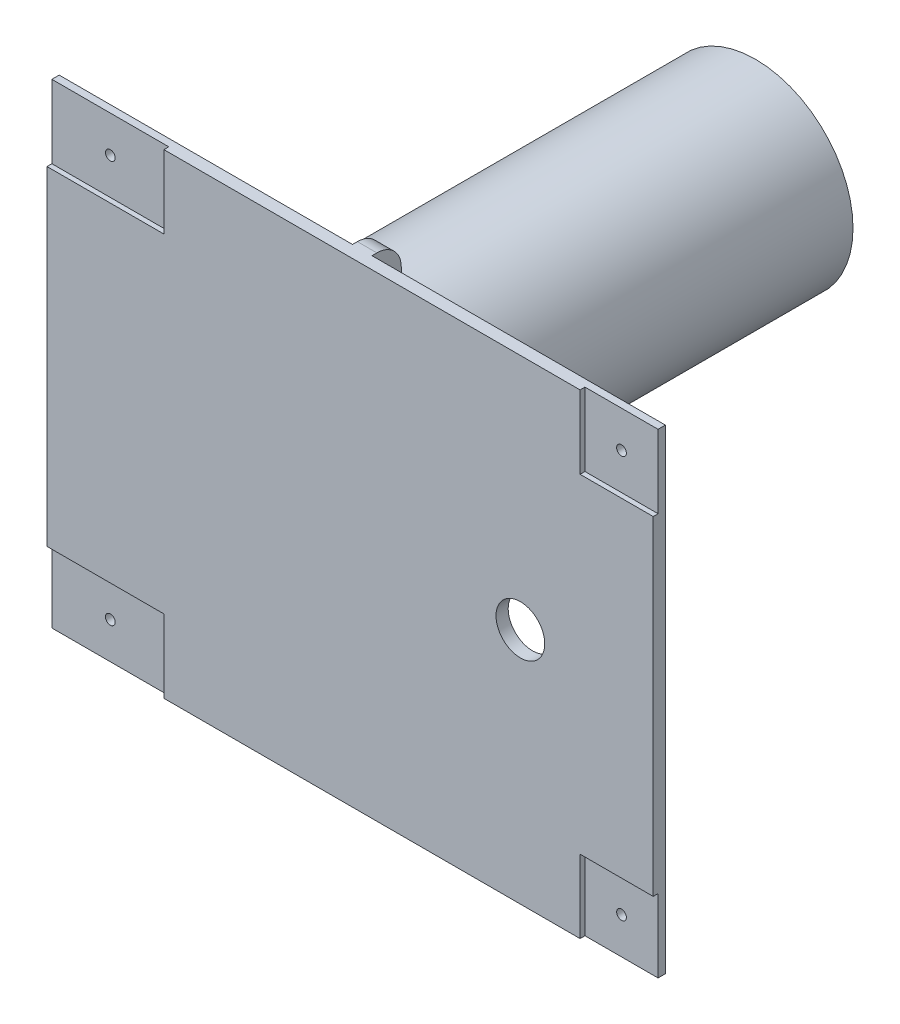
SolidWorks part; units mm, degrees
ref_plane "Alzado" through (0, 0, 0) normal (0, 0, 1) x (1, 0, 0)
ref_plane "Planta" through (0, 0, 0) normal (0, 1, 0) x (1, 0, 0)
ref_plane "Vista lateral" through (0, 0, 0) normal (1, 0, 0) x (0, 0, -1)
sketch "Croquis1" plane through (0, 0, 0) normal (0, 0, 1) x (1, 0, 0)
  line L1 (-117.2917, 97.7627) -> (131.4683, 97.7627)
  line L2 (-117.2917, 97.7627) -> (-117.2917, -97.2373)
  line L3 (-117.2917, -97.2373) -> (131.4683, -97.2373)
  line L4 (131.4683, 97.7627) -> (131.4683, -97.2373)
  dimension "D1" = 248.76
  dimension "D2" = 195
extrude "Saliente-Extruir1" add sketch "Croquis1" along normal blind 5
sketch "Croquis2" plane through (0, 0, 5) normal (0, 0, 1) x (1, 0, 0)
  line L0 (-117.2917, 0.2627) -> (131.4683, 0.2627) construction
  line L1 (-117.2917, 97.7627) -> (-117.2917, -97.2373) construction
  line L2 (131.4683, -97.2373) -> (131.4683, 97.7627) construction
  line L3 (-117.2917, -97.2373) -> (-69.2917, -97.2373)
  line L4 (-117.2917, -97.2373) -> (131.4683, -97.2373) construction
  line L5 (-69.2917, -97.2373) -> (-69.2917, -67.2373)
  line L6 (-69.2917, -67.2373) -> (-117.2917, -67.2373)
  line L7 (-117.2917, -67.2373) -> (-117.2917, -97.2373)
  line L8 (131.4683, 67.7627) -> (101.4683, 67.7627)
  line L9 (131.4683, -97.2373) -> (101.4683, -97.2373)
  line L10 (131.4683, -97.2373) -> (131.4683, -67.2373)
  line L11 (131.4683, -67.2373) -> (101.4683, -67.2373)
  line L12 (101.4683, -97.2373) -> (101.4683, -67.2373)
  line L13 (101.4683, 97.7627) -> (101.4683, 67.7627)
  line L14 (131.4683, 97.7627) -> (101.4683, 97.7627)
  line L15 (131.4683, 97.7627) -> (131.4683, 67.7627)
  line L16 (-69.2917, 67.7627) -> (-117.2917, 67.7627)
  line L17 (-69.2917, 97.7627) -> (-69.2917, 67.7627)
  line L18 (-117.2917, 97.7627) -> (-69.2917, 97.7627)
  line L19 (-117.2917, 67.7627) -> (-117.2917, 97.7627)
  dimension "D1" = 48
  dimension "D2" = 30
  dimension "D3" = 30
  dimension "D4" = 30
extrude "Cortar-Extruir1" cut sketch "Croquis2" against normal blind 2
sketch "Croquis3" plane through (0, 0, 5) normal (0, 0, 1) x (1, 0, 0)
  line L0 (-69.2917, 97.7627) -> (-117.2917, 97.7627) construction
  circle A0 centre (-93.2917, 82.7627) radius 2
  circle A1 centre (-93.2917, -82.2373) radius 2
  circle A2 centre (116.4683, 82.7627) radius 2
  circle A3 centre (116.4683, -82.2373) radius 2
  dimension "D2" = 4
  dimension "D3" = 4
  dimension "D5" = 4
  dimension "D6" = 4
  dimension "D1" = 15
  dimension "D4" = 15
  dimension "D7" = 209.76
  dimension "D8" = 165
extrude "Cortar-Extruir2" cut sketch "Croquis3" against normal blind 10
sketch "Croquis4" plane through (0, 0, 0) normal (0, 0, -1) x (-1, 0, 0)
  line L5 (-131.4683, -97.2373) -> (-131.4683, 97.7627) construction
  line L7 (-131.4683, 97.7627) -> (117.2917, 97.7627) construction
  circle A0 centre (37.5317, 0.2627) radius 40
  dimension "D3" = 80
  dimension "D1" = 169
  dimension "D2" = 97.5
extrude "Saliente-Extruir2" add sketch "Croquis4" along normal blind 206 contours A0
sketch "Croquis5" plane through (0, 0, 0) normal (0, 0, -1) x (-1, 0, 0)
  line L0 (-131.4683, 0.2627) -> (117.2917, 0.2627) construction
  line L1 (-131.4683, -97.2373) -> (-131.4683, 97.7627) construction
  line L2 (117.2917, 97.7627) -> (117.2917, -97.2373) construction
  circle A0 centre (-76.9683, 0.2627) radius 10
  dimension "D1" = 20
  dimension "D2" = 54.5
extrude "Cortar-Extruir3" cut sketch "Croquis5" against normal blind 10
sketch "Croquis6" plane through (0, 0, 0) normal (0, 0, -1) x (-1, 0, 0)
  line L0 (-131.4683, 97.7627) -> (117.2917, 97.7627) construction
  line L1 (-7.0883, 97.7627) -> (-7.0883, -97.2373)
  line L2 (117.2917, -97.2373) -> (-131.4683, -97.2373) construction
  line L3 (-7.0883, 97.7627) -> (117.2917, 97.7627)
  line L4 (117.2917, 97.7627) -> (117.2917, -97.2373)
  line L5 (117.2917, -97.2373) -> (-7.0883, -97.2373)
  circle A0 centre (-7.0883, 0.2627) radius 100
  dimension "D1" = 200
sketch "Croquis9" plane through (0, 97.7627, 0) normal (0, 1, 0) x (1, 0, 0)
  line L0 (7.0883, 0) -> (7.0883, -5)
  line L1 (131.4683, 0) -> (-117.2917, 0) construction
  line L2 (101.4683, -5) -> (-69.2917, -5) construction
ref_plane "Plano3" through (7.0883, 0, 0) normal (1, 0, 0) x (0, 0, -1)
sketch "Croquis12" plane through (7.0883, 0, 0) normal (1, 0, 0) x (0, 0, -1)
  line L0 (0, 97.7627) -> (0, 67.7627)
  line L1 (0, 67.7627) -> (12, 67.7627)
  line L2 (12, 67.7627) -> (12, 97.7627)
  line L3 (12, 97.7627) -> (0, 97.7627)
  line L4 (0, -97.2373) -> (12, -97.2373)
  line L5 (12, -97.2373) -> (12, -67.2373)
  line L6 (12, -67.2373) -> (0, -67.2373)
  line L7 (0, -67.2373) -> (0, -97.2373)
  dimension "D1" = 30
  dimension "D2" = 12
  dimension "D3" = 30
  dimension "D4" = 12
extrude "Saliente-Extruir3" add sketch "Croquis12" along normal mid plane 8
fillet "Redondeo1" radius 10 2 edges at (7.0883, -67.2373, 0) (7.0883, 67.7627, 0)
fillet "Redondeo2" radius 10 2 edges at (7.0883, 67.7627, -12) (7.0883, -67.2373, -12)
fillet "Redondeo3" radius 10 2 edges at (7.0883, -97.2373, -12) (7.0883, 97.7627, -12)
sketch "Croquis13" plane through (11.0883, 0, 0) normal (1, 0, 0) x (0, 0, -1)
  line L0 (-5, 0.2627) -> (206, 0.2627) construction
  line L1 (-5, -67.2373) -> (-5, 67.7627) construction
  line L2 (206, -39.7373) -> (206, 40.2627) construction
  line L3 (6, 87.7627) -> (12, 87.7627) construction
  line L4 (6, 87.7627) -> (6, 77.7627) construction
  circle A0 centre (6, 87.7627) radius 1.625
  circle A1 centre (6, 77.7627) radius 1.625
  circle A2 centre (6, -77.2373) radius 1.625
  circle A3 centre (6, -87.2373) radius 1.625
  dimension "D3" = 3.25
  dimension "D4" = 3.25
  dimension "D1" = 6
extrude "Cortar-Extruir5" cut sketch "Croquis13" against normal through all both and the other way through all
sketch "Croquis14" plane through (0, 0, 0) normal (0, 0, -1) x (-1, 0, 0)
  line L0 (-7.0883, 97.7627) -> (-7.0883, -97.2373)
  line L1 (-7.0883, 97.7627) -> (117.2917, 97.7627)
  line L2 (117.2917, 97.7627) -> (117.2917, -97.2373)
  line L3 (117.2917, -97.2373) -> (-7.0883, -97.2373)
